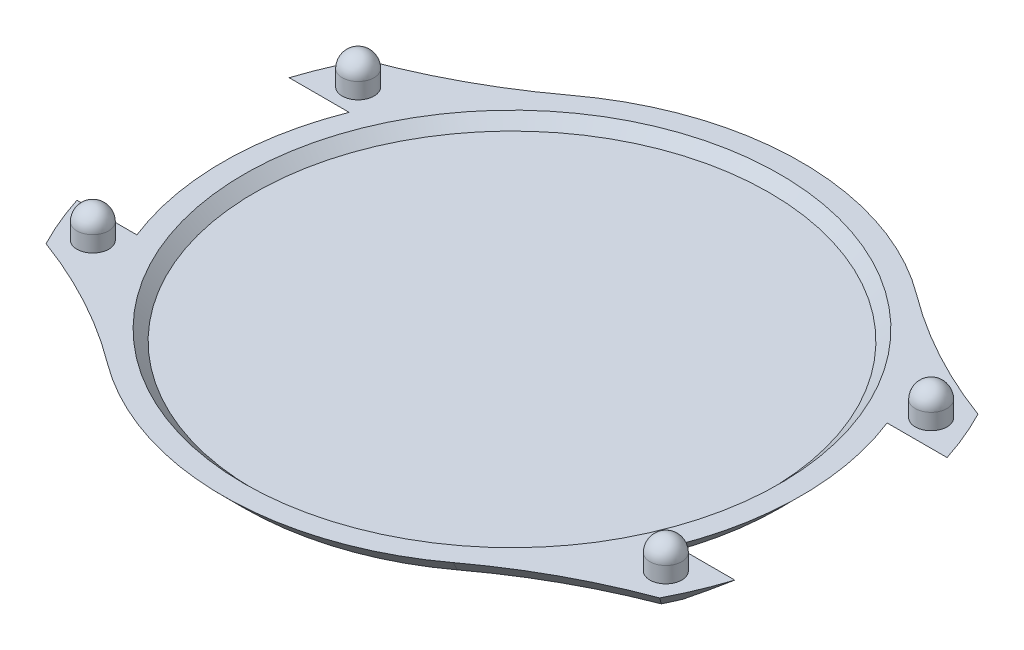
SolidWorks part; units mm, degrees
ref_plane "Front Plane" through (0, 0, 0) normal (0, 0, 1) x (1, 0, 0)
ref_plane "Top Plane" through (0, 0, 0) normal (0, 1, 0) x (1, 0, 0)
ref_plane "Right Plane" through (0, 0, 0) normal (1, 0, 0) x (0, 0, -1)
sketch "Sketch1" plane through (0, 0, 0) normal (0, 1, 0) x (1, 0, 0)
  line L0 (-31, 10) -> (-25.3488, 10)
  line L1 (-31, -10) -> (-25.3488, -10)
  line L2 (31, -10) -> (25.3488, -10)
  line L3 (31, 10) -> (25.3488, 10)
  arc A0 (-31, 10) -> (-28.9137, 15) centre (0, 0) cw
  arc A1 (-28.9137, 15) -> (-16.2928, 21.8428) centre (-46.188, 61.9212) ccw
  arc A2 (31, 10) -> (28.9137, 15) centre (0, 0) ccw
  arc A3 (28.9137, 15) -> (16.2928, 21.8428) centre (46.188, 61.9212) cw
  arc A4 (-16.2928, 21.8428) -> (16.2928, 21.8428) centre (0, 0) cw
  arc A5 (-31, -10) -> (-28.9137, -15) centre (0, 0) ccw
  arc A6 (-28.9137, -15) -> (-16.2928, -21.8428) centre (-46.188, -61.9212) cw
  arc A7 (-16.2928, -21.8428) -> (16.2928, -21.8428) centre (0, 0) ccw
  arc A8 (16.2928, -21.8428) -> (28.9137, -15) centre (46.188, -61.9212) cw
  arc A9 (28.9137, -15) -> (31, -10) centre (0, 0) ccw
  arc A10 (25.3488, -10) -> (25.3488, 10) centre (0, 0) ccw
  arc A11 (-25.3488, -10) -> (-25.3488, 10) centre (0, 0) cw
  circle A12 centre (0, 0) radius 25.25
  circle A13 centre (-27, 12.5) radius 1.5
  circle A14 centre (-27, -12.5) radius 1.5
  circle A15 centre (27, -12.5) radius 1.5
  circle A16 centre (27, 12.5) radius 1.5
extrude "Boss-Extrude2" add sketch "Sketch1" along normal blind 2
sketch "Sketch2" plane through (0, 0, 0) normal (0, -1, 0) x (1, 0, 0)
  circle A0 centre (0, 0) radius 25.25
extrude "Boss-Extrude3" add sketch "Sketch2" against normal blind 2
sketch "Sketch3" plane through (0, 2, 0) normal (0, 1, 0) x (1, 0, 0)
  circle A0 centre (0, 0) radius 25.25
  dimension "D1" = 50.5
extrude "Cut-Extrude1" cut sketch "Sketch3" against normal blind 1
sketch "Sketch4" plane through (0, 0, 0) normal (0, -1, 0) x (1, 0, 0)
  circle A0 centre (27, -12.5) radius 1.5
  circle A1 centre (27, 12.5) radius 1.5
  circle A2 centre (-27, 12.5) radius 1.5
  circle A3 centre (-27, -12.5) radius 1.5
extrude "Boss-Extrude4" add sketch "Sketch4" against normal blind 5
fillet "Fillet1" radius 1.5 4 edges at (27, 5, -14) (27, 5, 11) (-27, 5, 11) (-27, 5, -14)
chamfer "Chamfer1" distance 2 angle 45 16 edges at (-28.1744, 0, -10) (-27.25, 0, 0) (-28.1744, 0, 10) (-30.061, 0, 12.5435) (-22.3564, 0, 17.966) (0, 0, 27.25) (22.3564, 0, 17.966) (30.061, 0, 12.5435) (28.1744, 0, 10) (27.25, 0, 0) (28.1744, 0, -10) (30.061, 0, -12.5435) (22.3564, 0, -17.966) (0, 0, -27.25) (-22.3564, 0, -17.966) (-30.061, 0, -12.5435)
chamfer "Chamfer2" distance 1 angle 45 1 edges at (0, 1, 25.25)
